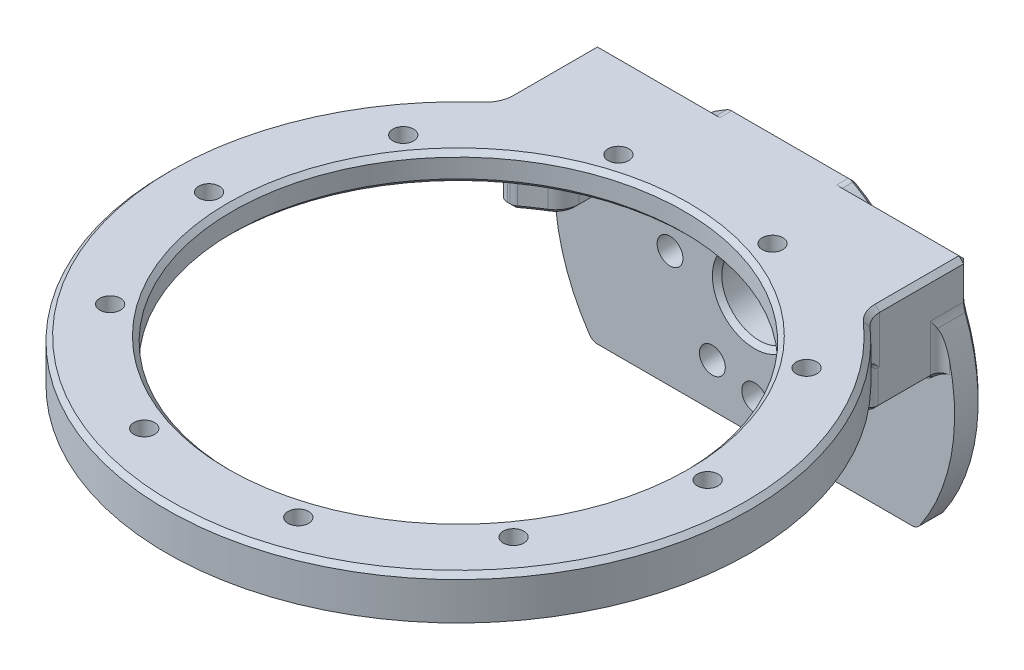
SolidWorks part; units mm, degrees
material "7075-T6 (SN)"
ref_plane "前视基准面" through (0, 0, 0) normal (0, 0, 1) x (1, 0, 0)
ref_plane "上视基准面" through (0, 0, 0) normal (0, 1, 0) x (1, 0, 0)
ref_plane "右视基准面" through (0, 0, 0) normal (1, 0, 0) x (0, 0, -1)
sketch "草图5" plane through (0, 18.85, 0) normal (0, 1, 0) x (1, 0, 0)
  circle A1 centre (0, -71.5) radius 60 construction
  circle A2 centre (0, -71.5) radius 62
  circle A3 centre (0, -71.5) radius 62
  circle A4 centre (0, -71.5) radius 60
  dimension "D1" = 2
extrude "凸台-拉伸3" add sketch "草图5" against normal blind 3
sketch "草图6" plane through (0, 18.85, 0) normal (0, 1, 0) x (1, 0, 0)
  circle A0 centre (0, -71.5) radius 62 construction
  circle A1 centre (0, -71.5) radius 62
  circle A2 centre (0, -71.5) radius 53 construction
  circle A3 centre (0, -71.5) radius 48
  dimension "D1" = 5
extrude "凸台-拉伸4" add sketch "草图6" along normal blind 6
sketch "草图4" plane through (0, 0, 0) normal (0, 0, 1) x (1, 0, 0)
  line L0 (-60, 0) -> (60, 0) construction
  line L1 (59.5, 18.85) -> (0, 18.85) construction
  line L2 (31.0379, -18.85) -> (50.9974, -18.85) construction
  line L3 (38.091, 18.85) -> (-38.091, 18.85) construction
  line L4 (-38.091, -18.85) -> (38.091, -18.85) construction
  line L5 (34.4779, 24.85) -> (-34.4779, 24.85)
  line L6 (-34.4779, -24.85) -> (34.4779, -24.85)
  line L7 (59.5, 24.85) -> (0, 24.85) construction
  line L8 (59.5, 18.85) -> (0, 18.85) construction
  line L9 (-968.9621, -18.85) -> (50.9974, -18.85) construction
  line L10 (-968.9621, -24.85) -> (50.9974, -24.85) construction
  circle A0 centre (0, 0) radius 18 construction
  circle A4 centre (0, 0) radius 8
  circle A5 centre (0, 0) radius 42.5 construction
  arc A6 (-34.4779, 24.85) -> (-34.4779, -24.85) centre (0, 0) ccw
  arc A7 (34.4779, -24.85) -> (34.4779, 24.85) centre (0, 0) ccw
  dimension "D1" = 6
  dimension "D2" = 6
  dimension "D4" = 10
sketch "草图7" plane through (0, 0, 0) normal (0, 0, 1) x (1, 0, 0)
  circle A2 centre (0, 0) radius 28
  circle A3 centre (0, 0) radius 28
  circle A4 centre (0, 0) radius 8
  circle A5 centre (0, 0) radius 8
  dimension "D1" = 10
  dimension "D2" = 10
extrude "凸台-拉伸5" add sketch "草图7" along normal blind 2.5 separate body
extrude "凸台-拉伸6" add sketch "草图4" along normal blind 6 from offset 2.5
sketch "草图9" plane through (0, 0, 8.5) normal (0, 0, 1) x (1, 0, 0)
  line L1 (-39.4338, 15.85) -> (-39.4338, 24.85)
  line L2 (62, 15.85) -> (-62, 15.85)
  line L3 (62, 15.85) -> (-62, 15.85)
  line L4 (62, 24.85) -> (-62, 24.85) construction
  line L5 (-39.4338, 24.85) -> (-34.4779, 24.85)
  line L6 (39.4137, 15.85) -> (39.4137, 24.85)
  line L7 (39.4137, 24.85) -> (34.4779, 24.85)
  arc A0 (-34.4779, 24.85) -> (-34.4779, -24.85) centre (0, 0) ccw construction
  arc A1 (34.4779, -24.85) -> (34.4779, 24.85) centre (0, 0) ccw construction
  arc A2 (-34.4779, 24.85) -> (-34.4779, -24.85) centre (0, 0) ccw
  arc A3 (34.4779, -24.85) -> (34.4779, 24.85) centre (0, 0) ccw
  arc M2 (-34.4779, 24.85) -> (-34.4779, -24.85) centre (0, 0) ccw
  arc M4 (34.4779, -24.85) -> (34.4779, 24.85) centre (0, 0) ccw
  dimension "D1" = 9
extrude "凸台-拉伸7" add sketch "草图9" against normal blind 6 contours L5 L1 M2 | L6 L7 M4 region at (37.8437, 22.0173, 8.5) region at (-37.8578, 22.0025, 8.5)
sketch "草图10" plane through (0, 24.85, 0) normal (0, 1, 0) x (1, 0, 0)
  line L0 (-39.4338, -8.5) -> (-39.4338, -23.6568)
  line L1 (39.4137, -8.5) -> (39.4137, -23.6402)
  line L2 (39.4137, -8.5) -> (-39.4338, -8.5) construction
  line L3 (39.4137, -8.5) -> (-39.4338, -8.5)
  circle A0 centre (0, -71.5) radius 62 construction
  circle A1 centre (0, -71.5) radius 62
  circle M1 centre (0, -71.5) radius 62
extrude "凸台-拉伸8" add sketch "草图10" against normal blind 9 contours L1 L3 L0 M1 region at (-0.0101, 24.85, 9.3029)
sketch "草图11" plane through (-39.4338, 0, 0) normal (-1, 0, 0) x (0, 0, 1)
  line L0 (8.5, 15.85) -> (23.6568, 15.85)
  line L1 (23.6568, 15.85) -> (23.6568, 5.85)
  line L2 (23.6568, 5.85) -> (8.5, 5.85)
  line L3 (8.5, -24.85) -> (8.5, 15.85) construction
  line L4 (8.5, 5.85) -> (8.5, 15.85)
extrude "凸台-拉伸9" add sketch "草图11" against normal up to surface (78.8476 mm away) up to face at (39.4137, 18.8666, 11.5467)
sketch "草图18" plane through (0, 18.85, 0) normal (0, -1, 0) x (1, 0, 0)
  circle A1 centre (0, 71.5) radius 60
  circle A2 centre (0, 71.5) radius 60
  dimension "D1" = 0
extrude "切除-拉伸6" cut sketch "草图18" along normal blind 20
sketch "草图19" plane through (0, 0, 0) normal (0, 0, -1) x (-1, 0, 0)
  circle A0 centre (0, 0) radius 8 construction
  circle A1 centre (0, 0) radius 8
extrude "切除-拉伸7" cut sketch "草图19" against normal blind 20
sketch "草图20" plane through (0, 5.85, 0) normal (0, -1, 0) x (1, 0, 0)
  line L0 (-39.4338, 8.5) -> (-29.4338, 8.5) construction
  line L1 (-39.4338, 8.5) -> (-5.4569, 8.5) construction
  line L2 (-29.4338, 8.5) -> (-29.4338, 23.6568)
  line L3 (39.4137, 8.5) -> (29.4137, 8.5) construction
  line L4 (39.4137, 8.5) -> (5.4569, 8.5) construction
  line L5 (29.4137, 8.5) -> (29.4137, 23.6568)
  line L6 (29.4137, 23.6568) -> (-29.4338, 23.6568)
  line L7 (-29.4338, 8.5) -> (29.4137, 8.5)
extrude "切除-拉伸8" cut sketch "草图20" against normal up to surface (13 mm away) up to face at (0, 18.85, 119.5)
fillet "圆角8" radius 5 4 edges at (-29.4338, 12.35, 19.2157) (29.4137, 12.35, 19.2044) (29.4137, 12.35, 8.5) (-29.4338, 12.35, 8.5)
fillet "圆角10" radius 5 2 edges at (-39.4338, 20.35, 23.6568) (39.4137, 20.35, 23.6402)
fillet "圆角11" radius 2 4 edges at (-36.2081, 10.85, 23.6568) (36.2081, 10.85, 23.6568) (39.4137, 10.85, 23.6568) (-39.4338, 10.85, 23.6568)
chamfer "倒角2" distance 1 angle 45 1 edges at (0, 15.85, 131.5)
chamfer "倒角3" distance 1 angle 45 2 edges at (0, 24.85, 119.5) (0, 18.85, 119.5)
sketch "草图21" plane through (0, 0, 2.5) normal (0, 0, 1) x (1, 0, 0)
  line L0 (12.9026, -24.85) -> (-12.9026, -24.85) construction
  line L1 (-12.9026, 24.85) -> (12.9026, 24.85) construction
  line L2 (12.9026, -24.85) -> (-12.9026, -24.85)
  line L3 (-12.9026, 24.85) -> (12.9026, 24.85)
  arc A0 (-12.9026, -24.85) -> (12.9026, -24.85) centre (0, 0) ccw construction
  arc A1 (12.9026, 24.85) -> (-12.9026, 24.85) centre (0, 0) ccw construction
  arc A2 (-12.9026, -24.85) -> (12.9026, -24.85) centre (0, 0) ccw
  arc A3 (12.9026, 24.85) -> (-12.9026, 24.85) centre (0, 0) ccw
extrude "切除-拉伸9" cut sketch "草图21" against normal blind 20
fillet "圆角13" radius 2 2 edges at (39.4137, 10.875, 8.5) (-39.4338, 10.85, 8.5)
fillet "圆角14" radius 5 2 edges at (-39.4338, 15.85, 6.5) (39.4137, 15.8999, 6.5)
fillet "圆角15" radius 2 2 edges at (-34.4779, -24.85, 5.5) (34.4779, -24.85, 5.5)
fillet "圆角16" radius 2 4 edges at (12.9026, 24.85, 1.25) (-12.9026, 24.85, 1.25) (-12.9026, -24.85, 1.25) (12.9026, -24.85, 1.25)
chamfer "倒角4" distance 1 angle 45 27 edges at (8, 0, 0) (8, 0, 8.5) (25.9092, 24.85, 2.5) (39.4137, 24.85, 11.918) (39.8546, 24.85, 23.3888) (0.0124, 24.85, 133.5) (-39.8742, 24.85, 23.4057) (-25.9193, 24.85, 2.5) (-39.4338, 24.85, 11.9269) (-39.4338, 20.8197, 2.5) (-39.5152, 15.8911, 2.5) (-42.1989, -5.0496, 2.5) (-34.372, -24.6187, 2.5) (-22.9216, -24.85, 2.5) (39.4137, 20.8463, 2.5) (39.4956, 15.9413, 2.5) (42.202, -5.0244, 2.5) (34.372, -24.6187, 2.5) (22.9216, -24.85, 2.5) (-28, 0, 0) (-12.897, -24.7885, 0) (-12.897, 24.7885, 0) (0, -24.85, 0) (0, 24.85, 0) (12.897, -24.7885, 0) (12.897, 24.7885, 0) (28, 0, 0)
chamfer "倒角5" distance 1 angle 45 18 edges at (-40.0196, 5.85, 9.0858) (-39.4338, 5.85, 16.0784) (-38.8481, 5.85, 23.071) (-37.1537, 5.85, 23.6568) (-36.2473, 5.85, 23.5562) (-33.7606, 5.85, 21.8994) (-30.061, 5.85, 18.7945) (-27.9694, 5.85, 9.9645) (-29.4338, 5.85, 14.935) (39.9995, 5.85, 9.0858) (39.4137, 5.85, 16.0784) (38.8279, 5.85, 23.071) (37.1436, 5.85, 23.6568) (36.2473, 5.85, 23.5562) (27.9493, 5.85, 9.9645) (33.7516, 5.85, 21.8932) (29.4137, 5.85, 14.9288) (30.0413, 5.85, 18.7828)
sketch "草图22" plane through (0, 0, 8.5) normal (0, 0, 1) x (1, 0, 0)
  circle A0 centre (0, 0) radius 18 construction
  circle A1 centre (0, -18) radius 2.75
  circle A2 centre (-9, -15.5885) radius 2.75
  circle A4 centre (-18, 0) radius 2.75
  circle A5 centre (-15.5885, 9) radius 2.75
  circle A9 centre (15.5885, 9) radius 2.75
  circle A10 centre (18, 0) radius 2.75
  circle A12 centre (9, -15.5885) radius 2.75
  circle A13 centre (-15.5885, -9) radius 2.75 [skipped]
  circle A14 centre (15.5885, -9) radius 2.75 [skipped]
  circle A15 centre (0, 18) radius 2.75 [skipped]
  circle A16 centre (-9, 15.5885) radius 2.75 [skipped]
  circle A17 centre (9, 15.5885) radius 2.75 [skipped]
  point P3 (0, -18)
  point P4 (-9, -15.5885)
  point P7 (-15.5885, -9)
  point P8 (-18, 0)
  point P9 (-15.5885, 9)
  point P10 (-9, 15.5885)
  point P11 (0, 18)
  point P12 (9, 15.5885)
  point P13 (15.5885, 9)
  point P14 (18, 0)
  point P15 (15.5885, -9)
  point P16 (9, -15.5885)
  point P17 (0, 0)
  point P43 (0, 0)
  dimension "D1" = 12
  dimension "D2" = 12
extrude "切除-拉伸10" cut sketch "草图22" against normal blind 20
sketch "草图23" plane through (0, 0, 0) normal (0, 0, -1) x (-1, 0, 0)
  circle A0 centre (0, 0) radius 19.5 construction
  circle A1 centre (0, 19.5) radius 2.5
  circle A2 centre (-16.8875, -9.75) radius 2.5
  circle A3 centre (16.8875, -9.75) radius 2.5
  point P3 (0, 19.5)
  point P4 (16.8875, -9.75)
  point P7 (-16.8875, -9.75)
  point P8 (0, 0)
  dimension "D1" = 3
extrude "切除-拉伸11" cut sketch "草图23" against normal blind 4
chamfer "倒角6" distance 0.5 angle 45 3 edges at (14.3875, -9.75, 0) (-19.3875, -9.75, 0) (-2.5, 19.5, 0)
sketch "草图24" plane through (0, 24.85, 0) normal (0, 1, 0) x (1, 0, 0)
  circle A0 centre (0, -71.5) radius 53 construction
  circle A1 centre (53, -71.5) radius 2.2
  circle A2 centre (42.8779, -102.6526) radius 2.2
  circle A3 centre (16.3779, -121.906) radius 2.2
  circle A4 centre (-16.3779, -121.906) radius 2.2
  circle A5 centre (-42.8779, -102.6526) radius 2.2
  circle A6 centre (-53, -71.5) radius 2.2
  circle A7 centre (-42.8779, -40.3474) radius 2.2
  circle A8 centre (-16.3779, -21.094) radius 2.2
  circle A9 centre (16.3779, -21.094) radius 2.2
  circle A10 centre (42.8779, -40.3474) radius 2.2
  point P3 (53, -71.5)
  point P7 (45.8993, -98)
  point P8 (26.5, -117.3993)
  point P9 (0, -124.5)
  point P10 (-26.5, -117.3993)
  point P11 (-45.8993, -98)
  point P12 (-53, -71.5)
  point P13 (-45.8993, -45)
  point P14 (-26.5, -25.6007)
  point P15 (0, -18.5)
  point P16 (26.5, -25.6007)
  point P17 (45.8993, -45)
  point P18 (0, -71.5)
  point P43 (0, -71.5)
  dimension "D1" = 12
  dimension "D2" = 10
extrude "切除-拉伸12" cut sketch "草图24" against normal through all both and the other way through all
fillet "圆角18" radius 2 6 edges at (39.4137, 15.85, 21.4964) (-39.4338, 15.85, 21.5053) (38.9571, 15.85, 22.9289) (33.454, 5.85, 8.5) (-38.9719, 15.85, 22.9352) (-33.4741, 5.85, 8.5)
sketch "草图28" plane through (0, -24.85, 0) normal (0, -1, 0) x (1, 0, 0)
  line L0 (-32.5, 8.5) -> (-32.5, 2.5) construction
  line L1 (-14.6689, 2.5) -> (-33.4384, 2.5) construction
  line L2 (32.5, 8.5) -> (32.5, 2.5) construction
  line L3 (33.4384, 2.5) -> (14.6689, 2.5) construction
  line L4 (-32.5, 5.5) -> (-29.5, 5.5) construction
  line L5 (32.5, 5.5) -> (29.5, 5.5) construction
hole_wizard "M3 螺纹孔1" positions "草图31" profile "草图32" tap size "M3" standard "GB"
sketch "草图31" plane through (0, -24.85, 0) normal (0, -1, 0) x (-1, 0, 0)
  point P0 (29.5, -5.5)
  point P3 (-29.5, -5.5)
sketch "草图32" plane through (-29.5, -24.85, 5.5) normal (1, 0, 0) x (0, 0, -1)
  line L0 (0, 0) -> (0, 8.2511)
  line L1 (0, 8.2511) -> (1.25, 7.5)
  line L2 (1.25, 7.5) -> (1.25, 0)
  line L5 (1.25, 0) -> (0, 0)
  line L10 (0, 8.2511) -> (-1.25, 7.5) construction
  line L11 (0, -6.35) -> (0, 107.95) construction
  dimension "螺纹孔钻头直径" = 2.5
  dimension "螺纹孔钻头深度" = 7.5
  dimension "导头角度" = 118
cosmetic thread "孔螺蚊线1" parameters "D1"=6, "D2"=3
cosmetic thread "孔螺蚊线2" parameters "D1"=6, "D2"=3
